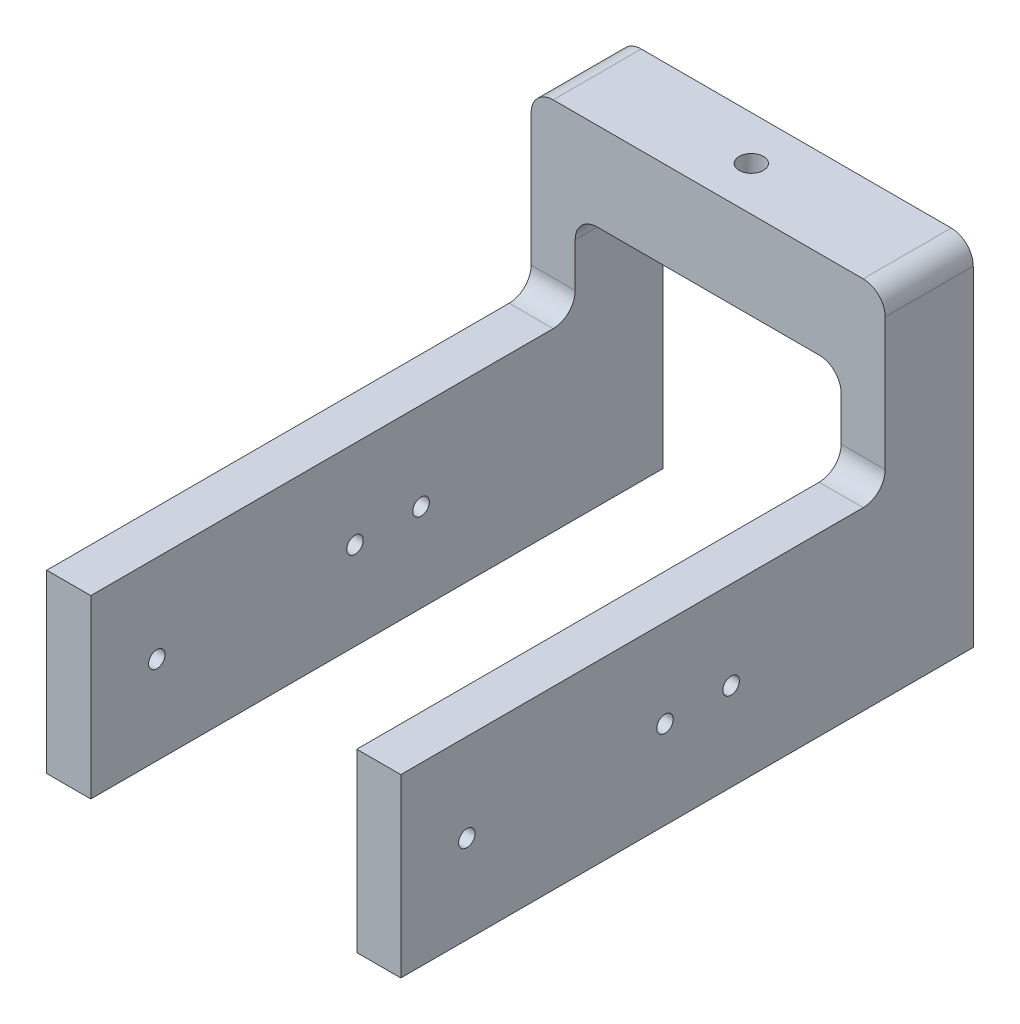
SolidWorks part; units mm, degrees
material "Galvanized Steel"
ref_plane "Front Plane" through (0, 0, 0) normal (0, 0, 1) x (1, 0, 0)
ref_plane "Top Plane" through (0, 0, 0) normal (0, 1, 0) x (1, 0, 0)
ref_plane "Right Plane" through (0, 0, 0) normal (1, 0, 0) x (0, 0, -1)
sketch "Sketch1" plane through (0, 0, 0) normal (1, 0, 0) x (0, 0, -1)
  line L0 (0, 0) -> (-165.1, 0)
  line L1 (-165.1, 0) -> (-165.1, 50.8)
  line L2 (-165.1, 50.8) -> (-25.4, 50.8)
  line L3 (-25.4, 50.8) -> (-25.4, 101.6)
  line L4 (-25.4, 101.6) -> (0, 101.6)
  line L5 (0, 101.6) -> (0, 0)
  point P7 (-12.7, 101.6)
  dimension "D1" = 152.4
  dimension "D2" = 50.8
  dimension "D3" = 101.6
  dimension "D4" = 25.4
extrude "Boss-Extrude1" add sketch "Sketch1" along normal blind 102.108
sketch "Sketch2" plane through (0, 0, 0) normal (0, 0, -1) x (-1, 0, 0)
  line L0 (-102.108, 0) -> (0, 0) construction
  line L1 (-89.408, 0) -> (-89.408, 76.2)
  line L2 (-89.408, 76.2) -> (-12.7, 76.2)
  line L3 (-12.7, 76.2) -> (-12.7, 0)
  line L4 (-12.7, 0) -> (-89.408, 0)
  line L5 (-102.108, 0) -> (-102.108, 101.6) construction
  line L6 (0, 0) -> (0, 101.6) construction
  line L7 (-102.108, 101.6) -> (0, 101.6) construction
  dimension "D1" = 12.7
  dimension "D2" = 12.7
  dimension "D3" = 25.4
extrude "Cut-Extrude1" cut sketch "Sketch2" against normal through all
hole_wizard "Ø7.0mm Dowel Hole1" positions "Sketch3" profile "Sketch4" hole size "Ø1.0" standard "ANSI Metric" end condition through all
sketch "Sketch3" plane through (0, 101.6, 0) normal (0, 1, 0) x (1, 0, 0)
  point P0 (50.8, -12.7)
  dimension "D1" = 50.8
  dimension "D2" = 12.7
sketch "Sketch4" plane through (50.8, 101.6, 12.7) normal (1, 0, 0) x (0, 0, 1)
  line L0 (0, 0) -> (0, 101.6)
  line L1 (0, 101.6) -> (3.5, 101.6)
  line L2 (3.5, 101.6) -> (3.5, 0)
  line L5 (3.5, 0) -> (0, 0)
  line L11 (0, -6.35) -> (0, 107.95) construction
  dimension "Thru Hole Dia." = 7
  dimension "Thru Hole Depth" = 101.6
fillet "Fillet1" radius 6.35 6 edges at (89.408, 76.2, 12.7) (12.7, 76.2, 12.7) (6.35, 50.8, 25.4) (95.758, 50.8, 25.4) (102.108, 101.6, 12.7) (0, 101.6, 12.7)
sketch "Sketch5" plane through (102.108, 0, 0) normal (1, 0, 0) x (0, 0, -1)
  line L0 (-165.1, 25.4) -> (0, 25.4) construction
  line L1 (-165.1, 50.8) -> (-165.1, 0) construction
  line L2 (0, 0) -> (0, 95.25) construction
  circle A0 centre (-146.05, 25.4) radius 2.3813
  circle A1 centre (-88.9, 25.4) radius 2.3813
  circle A2 centre (-69.85, 25.4) radius 2.3813
  dimension "D1" = 4.7625
  dimension "D2" = 19.05
  dimension "D3" = 76.2
  dimension "D4" = 95.25
extrude "Cut-Extrude2" cut sketch "Sketch5" against normal through all
